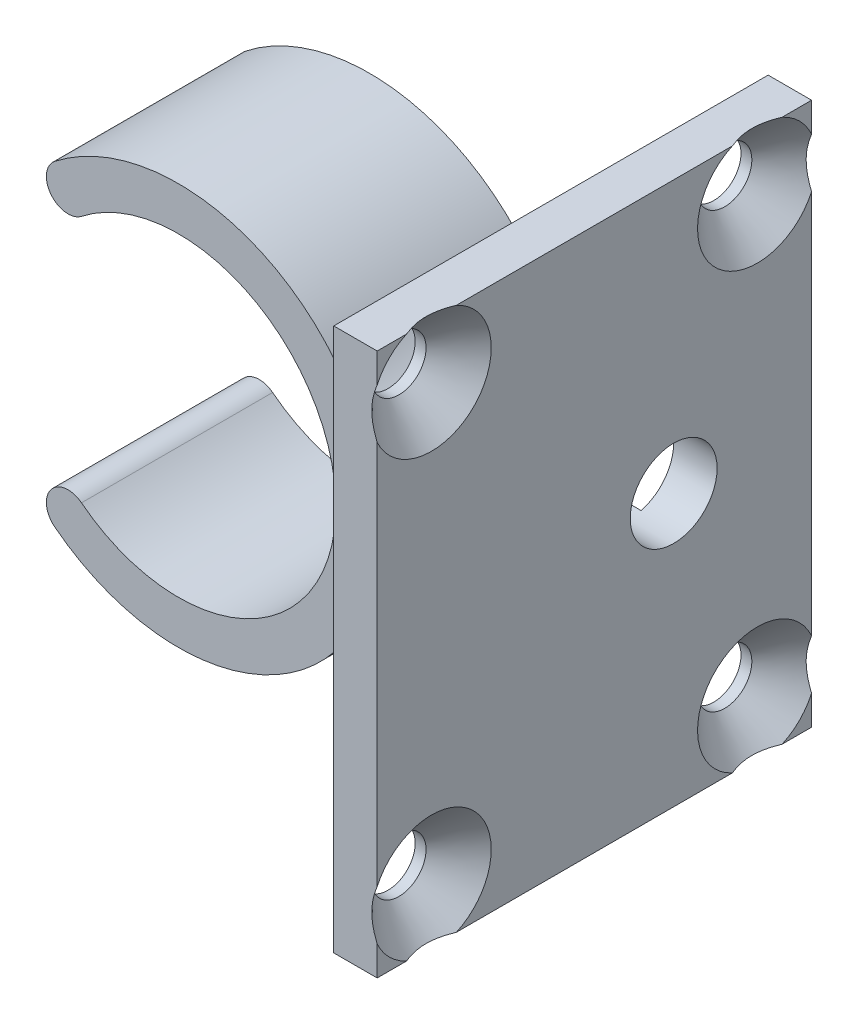
SolidWorks part; units mm, degrees
ref_plane "Спереди" through (0, 0, 0) normal (0, 0, 1) x (1, 0, 0)
ref_plane "Сверху" through (0, 0, 0) normal (0, 1, 0) x (1, 0, 0)
ref_plane "Справа" through (0, 0, 0) normal (1, 0, 0) x (0, 0, -1)
sketch "Эскиз1" plane through (0, 0, 0) normal (0, 0, 1) x (1, 0, 0)
  line L0 (9.25, 0) -> (0, 0) construction
  arc A0 (-4.4648, -5.7121) -> (-4.4648, 5.7121) centre (0, 0) ccw
  arc A1 (-5.6964, -7.2879) -> (-5.6964, 7.2879) centre (0, 0) ccw
  arc A2 (-5.6964, 7.2879) -> (-4.4648, 5.7121) centre (-5.0806, 6.5) ccw
  arc A3 (-5.6964, -7.2879) -> (-4.4648, -5.7121) centre (-5.0806, -6.5) cw
  dimension "D2" = 7.25
  dimension "D3" = 2
  dimension "D1" = 13
extrude "Выталкивающая часть (С ПАЗАМИ В ОБЕ СТОРОНЫ ВЫДАВИТЬ НА 5ММ)" add sketch "Эскиз1" along normal blind 4.8 and the other way blind 4
sketch "Эскиз2" plane through (0, 0, 0) normal (0, 0, 1) x (1, 0, 0)
  line L0 (0, 0) -> (22.4907, 0) construction
  line L11 (12.5, 3.75) -> (12.5, -3.75)
  arc A0 (7.2461, -5.7495) -> (7.2461, 5.7495) centre (0, 0) ccw
  arc A1 (-5.6964, -7.2879) -> (-5.6964, 7.2879) centre (0, 0) ccw construction
  arc A3 (7.2461, 5.7495) -> (12.5, 3.75) centre (11.5546, 9.1681) ccw
  arc A4 (7.2461, -5.7495) -> (12.5, -3.75) centre (11.5546, -9.1681) cw
  point P6 (12.5, 0)
  dimension "D1" = 7.5
  dimension "D3" = 12.5
  dimension "D2" = 5.5
extrude "Наплыв для крепления" add sketch "Эскиз2" along normal up to surface (4.8 mm away) and the other way up to surface (4 mm away) up to face at (1.1908, 0, 4.8) other way up to face at (1.1908, 0, -4)
sketch "Эскиз3" plane through (0, 0, 0) normal (0, 0, 1) x (1, 0, 0)
  line L0 (12.5, -12.5) -> (12.5, 12.5)
  line L1 (12.5, 12.5) -> (15.5, 12.5)
  line L2 (15.5, 12.5) -> (15.5, -12.5)
  line L3 (15.5, -12.5) -> (12.5, -12.5)
  line L5 (12.5, -3.75) -> (12.5, 3.75) construction
  point P9 (12.5, 0)
  point P10 (12.5, 0)
  dimension "D1" = 3
  dimension "D2" = 25
extrude "Пластина для фиксации" [suppressed] add sketch "Эскиз3" along normal blind 8.35 and the other way blind 8.35
sketch "Эскиз5" [suppressed] plane through (0, 12.5, 0) normal (0, 1, 0) x (1, 0, 0)
  line L0 (10.5, 8.35) -> (10.5, 7.35)
  line L1 (12.5, 8.35) -> (9.5, 8.35) construction
  line L2 (10.5, 7.35) -> (11.5, 7.35)
  line L3 (11.5, 7.35) -> (11.5, 8.35)
  line L4 (11.5, 8.35) -> (10.5, 8.35)
  line L5 (12.5, 0) -> (9.5, 0) construction
  line L6 (12.5, 8.35) -> (12.5, -8.35) construction
  line L7 (9.5, 5) -> (9.5, -5) construction
  line L8 (11.5, -8.35) -> (10.5, -8.35)
  line L9 (11.5, -7.35) -> (11.5, -8.35)
  line L10 (10.5, -7.35) -> (11.5, -7.35)
  line L11 (10.5, -8.35) -> (10.5, -7.35)
  point P7 (11, 8.35)
  point P8 (11, 8.35)
  dimension "D1" = 1
extrude "Пазы горизонтальные" [suppressed] cut sketch "Эскиз5" against normal through all
sketch "Эскиз6" [suppressed] plane through (12.5, 0, 0) normal (1, 0, 0) x (0, 0, -1)
  circle A0 centre (4.5, 0) radius 2
  dimension "D1" = 4
  dimension "D2" = 4.5
extrude "Под толкатель" [suppressed] cut sketch "Эскиз6" against normal through all
sketch "Эскиз7" [suppressed] plane through (0, 0, 8.35) normal (0, 0, 1) x (1, 0, 0)
  line L2 (11.3, 10.5) -> (11.3, 12.5)
  line L3 (12.5, 12.5) -> (9.5, 12.5) construction
  line L4 (11.3, 12.5) -> (12.5, 12.5)
  line L5 (12.5, 12.5) -> (12.5, 10.5)
  line L7 (12.5, 10.5) -> (11.3, 10.5)
  line L9 (12.5, -12.5) -> (12.5, 12.5) construction
  line L10 (0, 0) -> (12.5, 0) construction
  line L11 (12.5, -10.5) -> (11.3, -10.5)
  line L12 (12.5, -12.5) -> (12.5, -10.5)
  line L13 (11.3, -12.5) -> (12.5, -12.5)
  line L14 (11.3, -10.5) -> (11.3, -12.5)
  line L15 (9.5, 12.5) -> (9.5, -12.5) construction
  dimension "D1" = 2
  dimension "D2" = 1.8
extrude "Вертикальные пазы" [suppressed] cut sketch "Эскиз7" against normal through all
sketch "Эскиз8" plane through (12.5, 0, 0) normal (1, 0, 0) x (0, 0, -1)
  line L0 (-0.15, 12.5) -> (-0.15, -12.4045) construction
  line L1 (-10.15, 12.5) -> (9.85, 12.5)
  line L2 (-10.15, 12.5) -> (-10.15, -12.5)
  line L3 (-10.15, -12.5) -> (9.85, -12.5)
  line L4 (9.85, 12.5) -> (9.85, -12.5)
  line L5 (-10.15, 12.5) -> (9.85, -12.5) construction
  line L6 (-10.15, -12.5) -> (9.85, 12.5) construction
  line L7 (-10.15, 0) -> (9.85, 0) construction
  line L8 (-10.15, -12.5) -> (9.85, -12.5)
  line L9 (-4.8, -3.75) -> (-4.8, 3.75) construction
  circle A0 centre (-7.65, 10) radius 1.25
  circle A5 centre (-7.65, -10) radius 1.25
  circle A6 centre (7.35, -10) radius 1.25
  circle A7 centre (7.35, 10) radius 1.25
  point P0 (-0.15, 0)
  dimension "D4" = 2.5
  dimension "D1" = 25
  dimension "D2" = 20
  dimension "D3" = 4.65
  dimension "D5" = 2.5
  dimension "D6" = 2.5
extrude "Пластина для крепления на саморезы" add sketch "Эскиз8" along normal blind 2 contours L4 L1 L2 L3 A5 A0 A6 A7 region at (12.5, 0, 0.15)
chamfer "Фаска2" distance 1.5 angle 45 4 edges at (14.5, 10, 6.4) (14.5, -10, 6.4) (14.5, -10, -8.6) (14.5, 10, -8.6)
sketch "Эскиз9" plane through (14.5, 0, 0) normal (1, 0, 0) x (0, 0, -1)
  circle A0 centre (3.5, 0) radius 2
  dimension "D1" = 4
  dimension "D2" = 3.5
extrude "Вырез под толкатель" cut sketch "Эскиз9" against normal up to next
